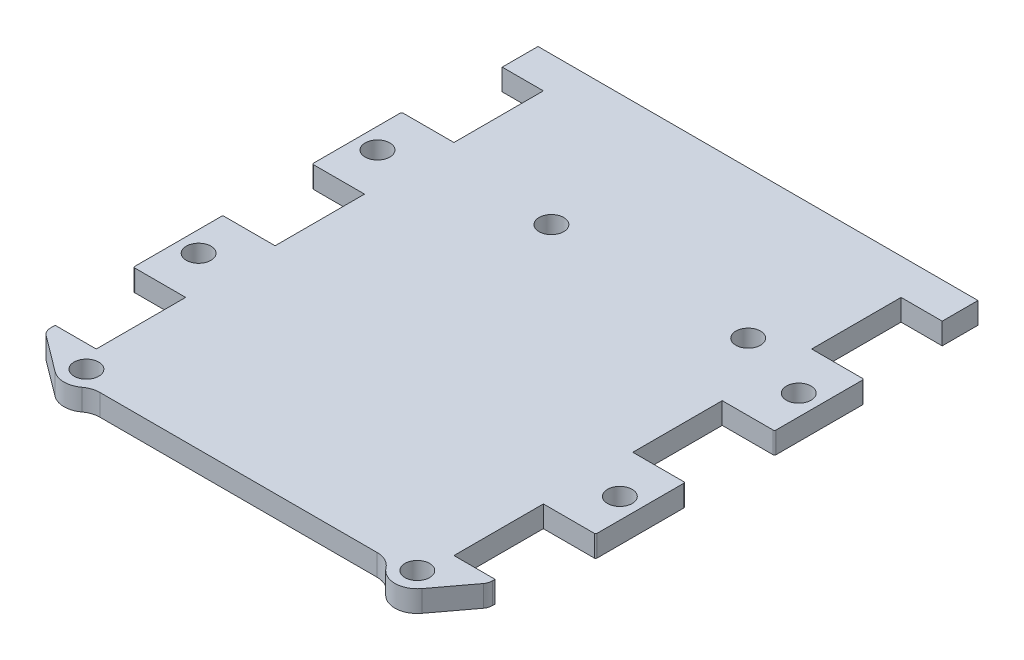
SolidWorks part; units mm, degrees
ref_plane "Front Plane" through (0, 0, 0) normal (0, 0, 1) x (1, 0, 0)
ref_plane "Top Plane" through (0, 0, 0) normal (0, 1, 0) x (1, 0, 0)
ref_plane "Right Plane" through (0, 0, 0) normal (1, 0, 0) x (0, 0, -1)
sketch "Sketch1" plane through (0, 0, 0) normal (0, 1, 0) x (1, 0, 0)
  line L0 (-31.242, -19.05) -> (-32.8295, -6.35) construction
  line L1 (31.242, -36.83) -> (-31.242, -36.83)
  line L2 (31.242, -36.83) -> (31.242, -31.75)
  line L3 (31.242, 36.83) -> (-31.242, 36.83)
  line L4 (-31.242, -36.83) -> (-31.242, -31.75)
  line L5 (0, 36.83) -> (0, -36.83) construction
  line L6 (31.242, 0) -> (-31.242, 0) construction
  line L7 (-25.4, -6.35) -> (-31.242, -6.35)
  line L8 (-25.4, -6.35) -> (-25.4, 6.35)
  line L9 (-25.4, 6.35) -> (-31.242, 6.35)
  line L10 (-25.4, -31.75) -> (-31.242, -31.75)
  line L11 (-28.321, 6.35) -> (-28.321, -6.35) construction
  line L12 (-25.4, 0) -> (-31.242, 0) construction
  line L13 (-25.4, -31.75) -> (-25.4, -19.05)
  line L14 (-25.4, -19.05) -> (-31.242, -19.05)
  line L15 (-28.321, -19.05) -> (-28.321, -31.75) construction
  line L16 (-25.4, -25.4) -> (-31.242, -25.4) construction
  line L17 (31.242, 6.35) -> (32.8295, 6.35)
  line L18 (-25.4, 25.4) -> (-31.242, 25.4) construction
  line L19 (-28.321, 19.05) -> (-28.321, 31.75) construction
  line L20 (-25.4, 19.05) -> (-31.242, 19.05)
  line L21 (-25.4, 31.75) -> (-25.4, 19.05)
  line L22 (-25.4, 31.75) -> (-31.242, 31.75)
  line L23 (-31.242, 31.75) -> (-31.242, 36.83)
  line L24 (-32.0357, 12.7) -> (-26.1937, 12.7) construction
  line L25 (28.321, 19.05) -> (28.321, 31.75) construction
  line L26 (25.4, 25.4) -> (31.242, 25.4) construction
  line L27 (25.4, -25.4) -> (31.242, -25.4) construction
  line L28 (28.321, -19.05) -> (28.321, -31.75) construction
  line L29 (25.4, 0) -> (31.242, 0) construction
  line L30 (28.321, 6.35) -> (28.321, -6.35) construction
  line L31 (25.4, 31.75) -> (31.242, 31.75)
  line L32 (25.4, 31.75) -> (25.4, 19.05)
  line L33 (25.4, 19.05) -> (31.242, 19.05)
  line L34 (25.4, -19.05) -> (31.242, -19.05)
  line L35 (25.4, -31.75) -> (25.4, -19.05)
  line L36 (25.4, -31.75) -> (31.242, -31.75)
  line L37 (25.4, 6.35) -> (31.242, 6.35)
  line L38 (25.4, -6.35) -> (25.4, 6.35)
  line L39 (25.4, -6.35) -> (31.242, -6.35)
  line L40 (32.0357, 12.7) -> (26.1937, 12.7) construction
  line L41 (31.242, 31.75) -> (31.242, 36.83)
  line L44 (-32.8295, -6.35) -> (-32.8295, -19.05)
  line L45 (-31.242, 19.05) -> (-32.8295, 19.05)
  line L46 (-31.242, -6.35) -> (-32.8295, -19.05) construction
  line L47 (-31.242, 6.35) -> (-32.8295, 6.35)
  line L48 (-32.8295, 19.05) -> (-32.8295, 6.35)
  line L49 (-31.242, 19.05) -> (-32.8295, 6.35) construction
  line L50 (-31.242, 6.35) -> (-32.8295, 19.05) construction
  line L51 (-31.242, -19.05) -> (-32.8295, -19.05)
  line L52 (-31.242, -6.35) -> (-32.8295, -6.35)
  line L53 (31.242, 6.35) -> (32.8295, 19.05) construction
  line L54 (31.242, 19.05) -> (32.8295, 6.35) construction
  line L55 (32.8295, 19.05) -> (32.8295, 6.35)
  line L56 (31.242, 19.05) -> (32.8295, 19.05)
  line L57 (31.242, -19.05) -> (32.8295, -19.05)
  line L58 (31.242, -6.35) -> (32.8295, -6.35)
  line L59 (31.242, -6.35) -> (32.8295, -19.05) construction
  line L60 (31.242, -19.05) -> (32.8295, -6.35) construction
  line L61 (32.8295, -6.35) -> (32.8295, -19.05)
  circle A0 centre (-29.9085, 12.7) radius 1.7526
  circle A1 centre (-29.9085, -12.7) radius 1.7526
  circle A2 centre (29.9085, -12.7) radius 1.7526
  circle A3 centre (29.9085, 12.7) radius 1.7526
  point P0 (0, 0)
  point P4 (-28.321, 0)
  point P9 (-28.321, -25.4)
  point P25 (-28.321, 25.4)
  point P67 (28.321, 25.4)
  point P68 (28.321, -25.4)
  point P69 (28.321, 0)
  point P76 (-32.0357, 12.7)
  dimension "D6" = 3.5052
  dimension "D1" = 62.484
  dimension "D2" = 73.66
  dimension "D3" = 5.842
  dimension "D4" = 12.7
  dimension "D7" = 1.5875
  dimension "D9" = 1.5875
  dimension "D5" = 2
  dimension "D8" = 2
  dimension "D10" = 2
extrude "Boss-Extrude1" add sketch "Sketch1" along normal blind 3.048
sketch "Sketch2" plane through (0, 3.048, 0) normal (0, 1, 0) x (1, 0, 0)
  line L0 (25.4, 19.05) -> (25.4, 31.75) construction
  circle A0 centre (19.558, 15.875) radius 1.7526
  circle A1 centre (29.9085, 12.7) radius 1.7526 construction
  circle A2 centre (-8.382, 15.875) radius 1.7526
  circle A3 centre (-23.622, -34.925) radius 1.7526
  circle A4 centre (24.638, -36.195) radius 1.7526
  dimension "D1" = 3.5052
  dimension "D5" = 3.5052
  dimension "D9" = 1.27
  dimension "D8" = 3.5052
  dimension "D2" = 5.842
  dimension "D3" = 3.175
  dimension "D6" = 15.24
  dimension "D7" = 50.8
  dimension "D10" = 48.26
  dimension "D4" = 2
extrude "Cut-Extrude1" cut sketch "Sketch2" against normal through all
sketch "Sketch3" plane through (0, 3.048, 0) normal (0, 1, 0) x (1, 0, 0)
  circle A0 centre (-23.622, -34.925) radius 3.175
  circle A1 centre (-23.622, -34.925) radius 1.7526
  circle A2 centre (24.638, -36.195) radius 1.7526
  circle A3 centre (24.638, -36.195) radius 3.175
  dimension "D1" = 6.35
  dimension "D2" = 6.35
extrude "Boss-Extrude2" add sketch "Sketch3" against normal up to surface (3.048 mm away) up to face at (-23.622, 0, 36.6776)
fillet "Fillet2" radius 0.2 8 edges at (-32.8295, 1.524, 19.05) (-32.8295, 1.524, 6.35) (-32.8295, 1.524, -19.05) (-32.8295, 1.524, -6.35) (32.8295, 1.524, -19.05) (32.8295, 1.524, -6.35) (32.8295, 1.524, 6.35) (32.8295, 1.524, 19.05)
fillet "Fillet3" radius 3.175 4 edges at (-26.162, 1.524, 36.83) (-21.082, 1.524, 36.83) (21.5271, 1.524, 36.83) (27.7489, 1.524, 36.83)
sketch "Sketch5" plane through (0, 3.048, 0) normal (0, 1, 0) x (1, 0, 0)
  line L0 (-25.527, -37.465) -> (-31.242, -33.1787)
  line L1 (-31.242, -31.75) -> (-31.242, -36.83) construction
  line L2 (-0.127, -36.83) -> (0, 36.83) construction
  line L3 (-19.812, -36.83) -> (19.558, -36.83) construction
  line L4 (31.242, 36.83) -> (-31.242, 36.83) construction
  line L5 (-31.242, -36.83) -> (-27.432, -36.83) construction
  line L6 (-31.242, -36.83) -> (-27.432, -36.83)
  line L7 (-31.242, -33.1787) -> (-31.242, -36.83)
  line L8 (27.178, -38.1) -> (31.242, -32.6813)
  line L9 (31.242, -36.83) -> (31.242, -31.75) construction
  line L10 (29.718, -36.83) -> (31.242, -36.83) construction
  line L11 (31.242, -36.83) -> (31.242, -32.6813)
  line L12 (29.718, -36.83) -> (31.242, -36.83)
  arc A0 (-25.527, -37.465) -> (-27.432, -36.83) centre (-27.432, -40.005) ccw construction
  arc A1 (-25.527, -37.465) -> (-27.432, -36.83) centre (-27.432, -40.005) ccw
  arc A2 (29.718, -36.83) -> (27.178, -38.1) centre (29.718, -40.005) ccw construction
  arc A3 (29.718, -36.83) -> (27.178, -38.1) centre (29.718, -40.005) ccw
extrude "Cut-Extrude2" cut sketch "Sketch5" against normal through all
fillet "Fillet4" radius 1.5875 2 edges at (-31.242, 1.524, 33.1787) (31.242, 1.524, 32.6813)
